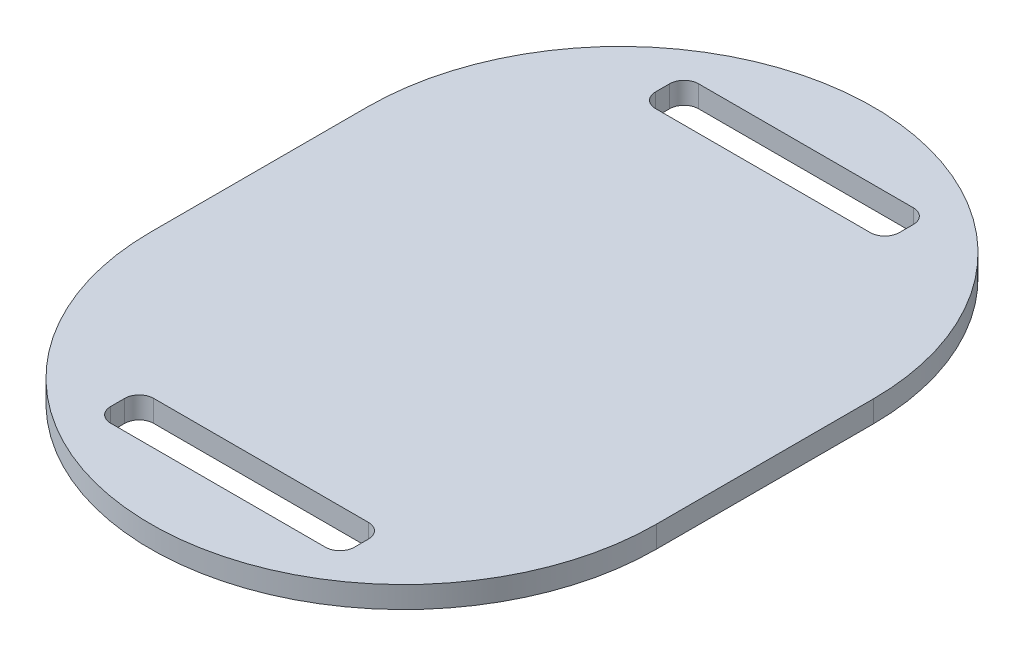
SolidWorks part; units mm, degrees
ref_plane "Front Plane" through (0, 0, 0) normal (0, 0, 1) x (1, 0, 0)
ref_plane "Top Plane" through (0, 0, 0) normal (0, 1, 0) x (1, 0, 0)
ref_plane "Right Plane" through (0, 0, 0) normal (1, 0, 0) x (0, 0, -1)
sketch "Sketch1" plane through (0, 0, 0) normal (0, 1, 0) x (1, 0, 0)
  line L0 (0, 0) -> (0, 76.2) construction
  line L1 (-88.9, 0) -> (-88.9, 76.2)
  line L2 (88.9, 0) -> (88.9, 76.2)
  arc A0 (-88.9, 0) -> (88.9, 0) centre (0, 0) ccw
  arc A1 (88.9, 76.2) -> (-88.9, 76.2) centre (0, 76.2) ccw
  point P3 (0, 38.1)
  dimension "D2" = 88.9
  dimension "D1" = 76.2
extrude "Boss-Extrude1" add sketch "Sketch1" along normal blind 7.62 contours A1 L1 A0 L2
sketch "Sketch2" plane through (0, 7.62, 0) normal (0, 1, 0) x (1, 0, 0)
  line L0 (0, 165.1) -> (0, -88.9) construction
  line L1 (-67.6572, 133.869) -> (67.6572, 133.869) construction
  line L3 (-67.6572, -57.669) -> (67.6572, -57.669) construction
  line L4 (-42.8387, -65.2307) -> (42.8387, -65.2307)
  line L5 (-42.8387, -65.2307) -> (-42.8387, -50.1072)
  line L6 (-42.8387, -50.1072) -> (42.8387, -50.1072)
  line L7 (42.8387, -65.2307) -> (42.8387, -50.1072)
  line L8 (-42.8387, -65.2307) -> (42.8387, -50.1072) construction
  line L9 (-42.8387, -50.1072) -> (42.8387, -65.2307) construction
  line L15 (-88.9, 38.1) -> (88.9, 38.1) construction
  line L16 (-88.9, 0) -> (-88.9, 76.2) construction
  line L17 (88.9, 0) -> (88.9, 76.2) construction
  line L18 (-42.8387, 141.4307) -> (42.8387, 126.3072) construction
  line L19 (-67.6572, 133.869) -> (67.6572, 133.869) construction
  line L20 (-42.8387, 126.3072) -> (42.8387, 141.4307) construction
  line L21 (42.8387, 141.4307) -> (42.8387, 126.3072)
  line L22 (-42.8387, 126.3072) -> (42.8387, 126.3072)
  line L23 (-42.8387, 141.4307) -> (-42.8387, 126.3072)
  line L24 (-42.8387, 141.4307) -> (42.8387, 141.4307)
  arc A0 (88.9, 76.2) -> (-88.9, 76.2) centre (0, 76.2) ccw construction
  arc A1 (-88.9, 0) -> (88.9, 0) centre (0, 0) ccw construction
  point P10 (0, -57.669)
extrude "Cut-Extrude1" cut sketch "Sketch2" against normal through all and the other way through all contours L6 L7 L4 L5 | L22 L21 L24 L23
fillet "Fillet1" radius 5.08 8 edges at (-42.8387, 3.81, -141.4307) (-42.8387, 3.81, -126.3072) (42.8387, 3.81, -141.4307) (42.8387, 3.81, -126.3072) (42.8387, 3.81, 50.1072) (42.8387, 3.81, 65.2307) (-42.8387, 3.81, 65.2307) (-42.8387, 3.81, 50.1072)
equation "\"MDF\"= 0.3in"
equation "\"D1@Boss-Extrude1\"=\"MDF\""
